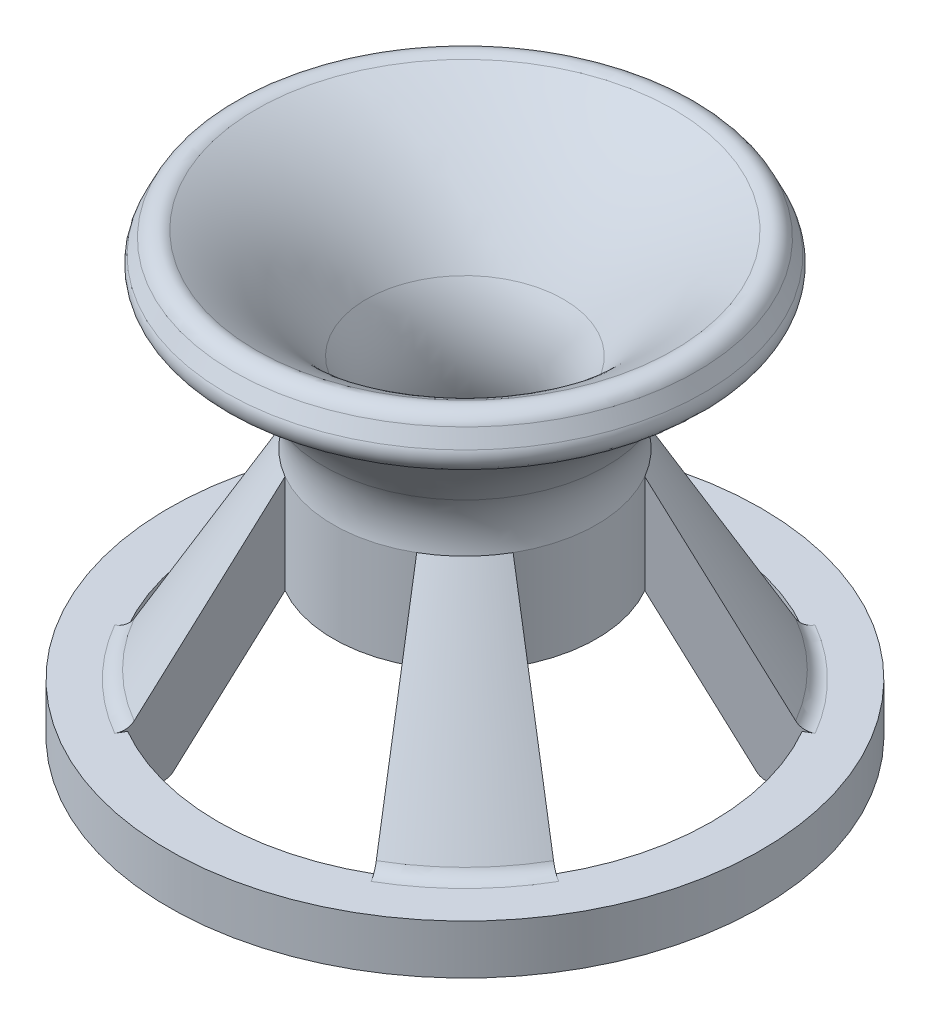
SolidWorks part; units mm, degrees
ref_plane "Front Plane" through (0, 0, 0) normal (0, 0, 1) x (1, 0, 0)
ref_plane "Top Plane" through (0, 0, 0) normal (0, 1, 0) x (1, 0, 0)
ref_plane "Right Plane" through (0, 0, 0) normal (1, 0, 0) x (0, 0, -1)
sketch "Sketch1" plane through (0, 0, 0) normal (0, 0, 1) x (1, 0, 0)
  line L0 (0, 0) -> (6.634, 0) construction
  line L1 (6.634, 0) -> (9, 0)
  line L2 (9, 0) -> (9, 1.5)
  line L3 (9, 1.5) -> (7.5, 1.5)
  line L4 (7.5, 1.5) -> (4, 7.5622)
  line L5 (4, 7.5622) -> (4, 10) construction
  line L6 (4, 10) -> (2.9954, 10) construction
  line L7 (2.9954, 10) -> (2.9954, 6.3022) construction
  line L8 (2.9954, 6.3022) -> (6.634, 0)
  line L9 (0, 0) -> (0, 10) construction
  line L10 (0, 10) -> (2.9954, 10) construction
  line L11 (-4, 10) -> (-2.9954, 10) construction
  line L12 (-4, 7.5622) -> (-4, 10) construction
  line L13 (-7.5, 1.5) -> (-4, 7.5622) construction
  line L14 (-9, 1.5) -> (-7.5, 1.5) construction
  line L15 (-9, 0) -> (-9, 1.5) construction
  line L16 (-6.634, 0) -> (-9, 0) construction
  line L17 (-2.9954, 6.3022) -> (-6.634, 0) construction
  line L18 (7.5, 0) -> (7.5, 1.5) construction
  line L19 (7.5, 1.5) -> (6.201, 0.75) construction
  line L20 (2.5, 8.1511) -> (4, 8.1511) construction
  line L26 (7.4724, 12.2265) -> (6.8089, 13.5718)
  line L28 (4.1922, 9.0498) -> (4.1922, 9.0498) construction
  line L29 (4.1922, 9.0498) -> (4.1922, 9.0498) construction
  line L30 (4.1922, 9.0498) -> (4.1922, 9.0498) construction
  line L31 (4.1922, 9.0498) -> (4.1922, 9.0498) construction
  line L32 (4.1922, 9.0498) -> (4.1922, 9.0498) construction
  arc A0 (2.9954, 10) -> (2.9954, 6.3022) centre (6.1978, 8.1511) ccw
  arc A1 (-2.9954, 10) -> (-2.9954, 6.3022) centre (-6.1978, 8.1511) cw construction
  arc A2 (2.9954, 10) -> (6.8089, 13.5718) centre (10.7896, 5.5) cw
  arc A4 (4.2945, 9.25) -> (7.4724, 12.2265) centre (10.7896, 5.5) cw
  arc A5 (4.2945, 9.25) -> (4, 7.5622) centre (6.4528, 8.0039) ccw
  arc A6 (4.2945, 9.25) -> (7.4724, 12.2265) centre (10.7896, 5.5) cw construction
  arc A7 (4.2945, 9.25) -> (4.1922, 9.0498) centre (6.1978, 8.1511) ccw construction
  point P22 (2.5, 8.1511)
  point P23 (-2.5, 8.1511)
  dimension "D9" = 9
  dimension "D1" = 18
  dimension "D2" = 5
  dimension "D3" = 1.5
  dimension "D4" = 10
  dimension "D5" = 60
  dimension "D6" = 15
  dimension "D8" = 5
  dimension "D7" = 1.5
revolve "Revolve1" add sketch "Sketch1" angle 360 about L9
sketch "Sketch2" plane through (0, 0, 0) normal (0, 1, 0) x (1, 0, 0)
  line L0 (-3.75, 6.4952) -> (-2, 3.4641)
  line L1 (2, 3.4641) -> (3.75, 6.4952)
  line L2 (0, 0) -> (0, 7.5) construction
  line L3 (6.4952, 3.75) -> (3.4641, 2)
  line L4 (3.4641, -2) -> (6.4952, -3.75)
  line L5 (3.75, -6.4952) -> (2, -3.4641)
  line L6 (-2, -3.4641) -> (-3.75, -6.4952)
  line L7 (-6.4952, -3.75) -> (-3.4641, -2)
  line L8 (-3.4641, 2) -> (-6.4952, 3.75)
  circle A1 centre (0, 0) radius 7.5
  arc A2 (3.75, 6.4952) -> (-3.75, 6.4952) centre (0, 0) ccw
  arc A3 (2, 3.4641) -> (-2, 3.4641) centre (0, 0) ccw
  arc A4 (6.4952, -3.75) -> (6.4952, 3.75) centre (0, 0) ccw
  arc A5 (3.4641, -2) -> (3.4641, 2) centre (0, 0) ccw
  arc A6 (-3.75, -6.4952) -> (3.75, -6.4952) centre (0, 0) ccw
  arc A7 (-2, -3.4641) -> (2, -3.4641) centre (0, 0) ccw
  arc A8 (-6.4952, 3.75) -> (-6.4952, -3.75) centre (0, 0) ccw
  arc A9 (-3.4641, 2) -> (-3.4641, -2) centre (0, 0) ccw
  point P23 (0, 0)
  dimension "D5" = 4
  dimension "D2" = 60
  dimension "D4" = 3.5
  dimension "D1" = 0
  dimension "D3" = 4
extrude "Cut-Extrude1" cut sketch "Sketch2" along normal up to vertex (7.5622 mm away) up to point (-4, 7.5622, 0)
fillet "Fillet1" radius 0.5 10 edges at (4.6909, 0, -4.6909) (4.6909, 0, 4.6909) (-4.6909, 0, 4.6909) (-4.6909, 0, -4.6909) (5.3033, 1.5, -5.3033) (5.3033, 1.5, 5.3033) (-5.3033, 1.5, -5.3033) (-5.3033, 1.5, 5.3033) (0, 12.2265, -7.4724) (0, 13.5718, -6.8089)
